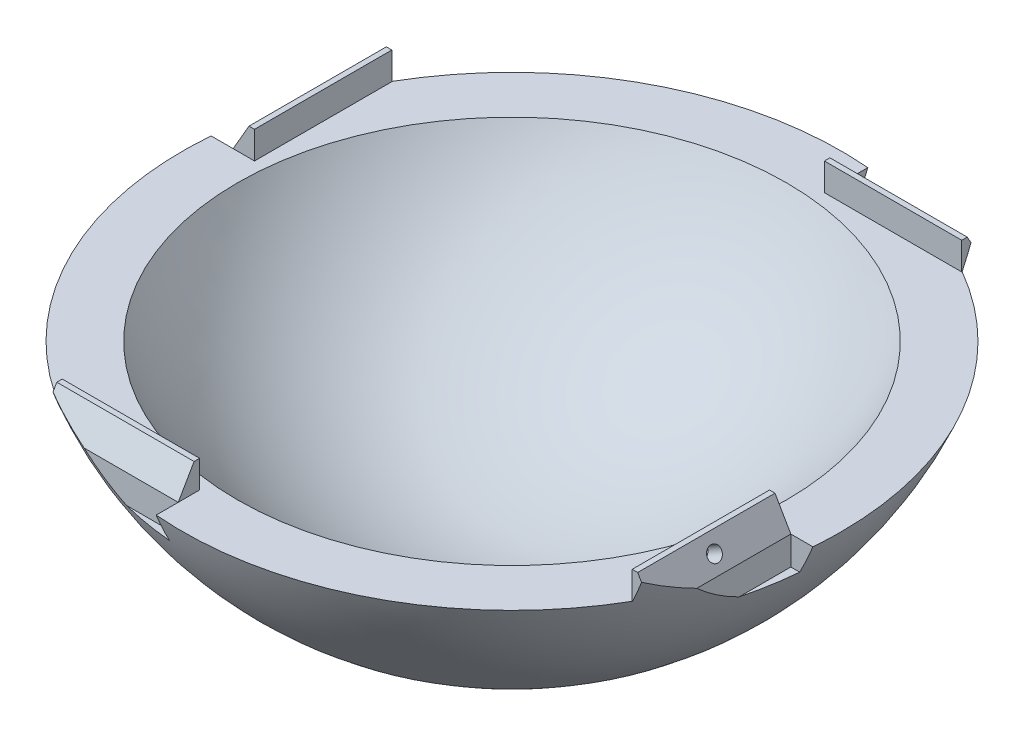
SolidWorks part; units mm, degrees
ref_plane "Front Plane" through (0, 0, 0) normal (0, 0, 1) x (1, 0, 0)
ref_plane "Top Plane" through (0, 0, 0) normal (0, 1, 0) x (1, 0, 0)
ref_plane "Right Plane" through (0, 0, 0) normal (1, 0, 0) x (0, 0, -1)
sketch "Sketch1" plane through (0, 0, 0) normal (0, 0, 1) x (1, 0, 0)
  line L0 (63.5, 0) -> (76.2, 0)
  line L1 (0, -63.5) -> (0, -76.2)
  line L2 (63.5, 0) -> (0, 0)
  line L3 (0, 0) -> (0, -50.8)
  line L4 (0, 0) -> (-76.2, 0)
  line L5 (0, 0) -> (0, -38.1)
  line L6 (0, 0) -> (-63.5, 0)
  line L7 (0, -50.8) -> (0, -51.2124)
  arc A0 (0, -76.2) -> (76.2, 0) centre (0, 0) ccw
  arc A1 (0, -63.5) -> (63.5, 0) centre (0, 0) ccw
  arc A2 (76.2, 0) -> (-76.2, 0) centre (0, 31.0836) cw
  arc A3 (-63.5, 0) -> (63.5, 0) centre (0, 33.6884) ccw
  dimension "D2" = 50.8
  dimension "D5" = 63.5
  dimension "D1" = 76.2
  dimension "D3" = 76.2
  dimension "D4" = 38.1
revolve "Revolve1" add sketch "Sketch1" angle 360 about L1
sketch "Sketch2" plane through (0, 0, 0) normal (0, 1, 0) x (1, 0, 0)
  line L0 (76.2, 0) -> (-76.2, 0)
  line L1 (-76.2, 6.35) -> (-63.5, 6.35)
  line L2 (-76.2, 0) -> (-63.5, 0)
  line L3 (-76.2, 0) -> (-76.2, 38.1)
  line L4 (-76.2, 38.1) -> (-63.5, 38.1)
  line L5 (-63.5, 0) -> (-63.5, 38.1)
  line L6 (-73.66, 0) -> (-73.66, 38.1)
  line L7 (-63.5, 38.1) -> (-50.8, 38.1)
  line L9 (-50.8, 38.1) -> (-63.5, 38.1)
  line L10 (-50.8, 38.1) -> (-50.8, 6.35)
  line L11 (-50.8, 6.35) -> (-63.5, 6.35)
  line L12 (-63.5, 38.1) -> (-63.5, 6.35)
  dimension "D1" = 10.16
  dimension "D2" = 2.54
  dimension "D3" = 38.1
  dimension "D4" = 6.35
extrude "Boss-Extrude2" add sketch "Sketch2" along normal blind 6.35
sketch "Sketch4" plane through (0, 6.35, 0) normal (0, 1, 0) x (1, 0, 0)
  line L0 (-63.5, 38.1) -> (-50.8, 38.1) construction
  line L1 (-50.8, 38.1) -> (-63.5, 38.1) construction
  line L2 (-50.8, 38.1) -> (-50.8, 6.35) construction
  line L3 (-50.8, 6.35) -> (-63.5, 6.35) construction
  line L4 (-73.66, 0) -> (-73.66, 38.1) construction
  line L5 (-76.2, 0) -> (-76.2, 38.1) construction
  line L6 (-76.2, 38.1) -> (-63.5, 38.1) construction
  line L7 (-76.2, 0) -> (-63.5, 0) construction
  line L8 (-63.5, 0) -> (-63.5, 38.1) construction
  line L9 (-63.5, 38.1) -> (-63.5, 6.35) construction
  line L10 (-76.2, 6.35) -> (-63.5, 6.35) construction
  line L11 (76.2, 0) -> (-76.2, 0) construction
  line L12 (-63.5, 38.1) -> (-50.8, 38.1)
  line L13 (-50.8, 38.1) -> (-63.5, 38.1)
  line L14 (-50.8, 38.1) -> (-50.8, 6.35)
  line L15 (-50.8, 6.35) -> (-63.5, 6.35)
  line L16 (-73.66, 0) -> (-73.66, 38.1)
  line L17 (-76.2, 0) -> (-76.2, 38.1)
  line L18 (-76.2, 38.1) -> (-63.5, 38.1)
  line L19 (-76.2, 0) -> (-63.5, 0)
  line L20 (-63.5, 0) -> (-63.5, 38.1)
  line L21 (-63.5, 38.1) -> (-63.5, 6.35)
  line L22 (-76.2, 6.35) -> (-63.5, 6.35)
  line L23 (76.2, 0) -> (-76.2, 0)
extrude "Cut-Extrude6" cut sketch "Sketch4" against normal blind 6.35
chamfer "Chamfer5" distance 12.7 angle 30 2 edges at (-63.5, 6.35, -22.225) (-63.5, 0, -22.225)
sketch "Sketch8" plane through (0, 0, 0) normal (0, 1, 0) x (1, 0, 0)
  line L0 (-70.8323, 6.35) -> (-75.935, 6.35)
  line L1 (-70.8323, 6.35) -> (-70.8323, 28.093) construction
  line L2 (-70.8323, 6.35) -> (-70.8323, 28.093)
  arc A0 (-70.8323, 28.093) -> (-65.9911, 38.1) centre (0, 0) ccw construction
  arc A1 (-70.8323, 28.093) -> (-65.9911, 38.1) centre (0, 0) ccw
  arc M1 (-70.8323, 28.093) -> (-65.9911, 38.1) centre (0, 0) ccw
  line M5 (-70.8323, 6.35) -> (-70.8323, 28.093)
extrude "Cut-Extrude11" cut sketch "Sketch8" against normal blind 6.604 contours L0 M5 M1
pattern_circular "CirPattern4" count 4 every 90 about axis through (0, 0, 0) along (0, 1, 0) of "Chamfer5", "Boss-Extrude2", "Cut-Extrude6", "Cut-Extrude11"
sketch "Sketch5" plane through (0, 6.35, 0) normal (0, 1, 0) x (1, 0, 0)
  line L0 (38.1, 65.8962) -> (6.35, 65.8962)
  line L1 (38.1, 65.9911) -> (38.1, 50.8) construction
  line L4 (38.1, 67.1662) -> (38.1, 50.8) construction
  line L6 (38.1, 67.1662) -> (38.1, 50.8)
  line L7 (38.1, 67.1662) -> (6.35, 67.1662) construction
  line L8 (6.35, 67.1662) -> (6.35, 63.1817) construction
  line L9 (6.35, 67.1662) -> (6.35, 63.1817)
  arc A2 (38.1, 50.8) -> (6.35, 63.1817) centre (0, 0) ccw construction
  arc A3 (38.1, 50.8) -> (6.35, 63.1817) centre (0, 0) ccw
  dimension "D1" = 1.27
extrude "Cut-Extrude7" cut sketch "Sketch5" against normal blind 6.35
pattern_circular "CirPattern5" count 4 every 90 about axis through (0, 0, 0) along (0, 1, 0) of "Cut-Extrude7"
sketch "Sketch11" plane through (53.1243, 30.6713, 0) normal (0.866, 0.5, 0) x (0, 0, -1)
  circle A0 centre (-22.225, -31.8476) radius 1.6383 construction
  circle A1 centre (-22.225, -31.8476) radius 1.6383
extrude "Cut-Extrude12" cut sketch "Sketch11" against normal blind 6.604
